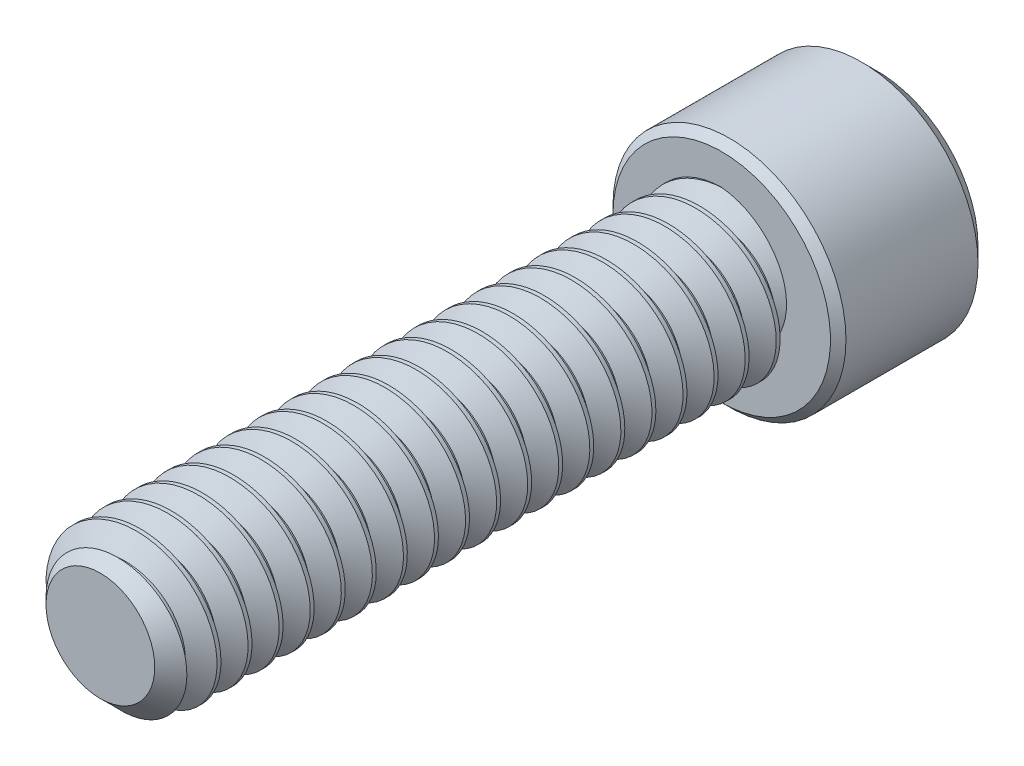
SolidWorks part; units mm, degrees
material "Plain Carbon Steel"
ref_plane "Front Plane" through (0, 0, 0) normal (0, 0, 1) x (1, 0, 0)
ref_plane "Top Plane" through (0, 0, 0) normal (0, 1, 0) x (1, 0, 0)
ref_plane "Right Plane" through (0, 0, 0) normal (1, 0, 0) x (0, 0, -1)
sketch "Sketch1" plane through (0, 0, 0) normal (0, 0, 1) x (1, 0, 0)
  line L0 (0, 3.175) -> (0, -3.175) construction
  circle A0 centre (0, 0) radius 3.175
  dimension "OD" = 6.35
extrude "Extrude1" add sketch "Sketch1" against normal blind 25.4
sketch "Sketch2" plane through (0, 0, 0) normal (0, 0, 1) x (1, 0, 0)
  circle A0 centre (0, 0) radius 3.175 construction
  circle A1 centre (0, 0) radius 3.175
curve "Helix/Spiral1" pitch 1.27 height 26.67 turns 21 parameters "pitch"=1.27
chamfer "Chamfer3" distance 0.9525 angle 45 1 edges at (3.175, 0, 0)
sketch "Sketch3" plane through (0, 0, 0) normal (1, 0, 0) x (0, 0, -1)
  line L0 (-1.1113, 3.175) -> (-0.635, 2.3501)
  line L1 (-0.635, 2.3501) -> (-0.4763, 2.3501)
  line L2 (-0.4763, 2.3501) -> (0, 3.175)
  line L3 (-1.1113, 3.175) -> (0, 3.175)
  line L4 (-0.5556, 3.175) -> (-0.5556, 2.3501) construction
  line L5 (-0.8731, 2.7626) -> (-0.2381, 2.7626) construction
  line L6 (0, 3.175) -> (0, -3.175) construction
  dimension "D1" = 0.1588
  dimension "D2" = 0.635
  dimension "D3" = 60
sweep "Cut-Sweep1" cut profiles "Sketch3" path "Helix/Spiral1"
sketch "Sketch6" plane through (0, 0, -25.4) normal (0, 0, -1) x (-1, 0, 0)
  circle A0 centre (0, 0) radius 4.7625
  dimension "head dia" = 9.525
extrude "Extrude2" add sketch "Sketch6" along normal blind 6.35
sketch "Sketch7" plane through (0, 0, -31.75) normal (0, 0, -1) x (-1, 0, 0)
  line L1 (0, 2.7496) -> (-2.3813, 1.3748)
  line L2 (-2.3813, 1.3748) -> (-2.3813, -1.3748)
  line L3 (-2.3813, -1.3748) -> (0, -2.7496)
  line L4 (0, -2.7496) -> (2.3813, -1.3748)
  line L5 (2.3813, -1.3748) -> (2.3813, 1.3748)
  line L6 (2.3813, 1.3748) -> (0, 2.7496)
  circle A0 centre (0, 0) radius 2.3813 construction
  dimension "hex dia" = 4.7625
extrude "Cut-Extrude1" cut sketch "Sketch7" against normal blind 3.5719
sketch "Sketch8" plane through (0, 0, -31.75) normal (0, 0, -1) x (-1, 0, 0)
  circle A0 centre (0, 0) radius 2.7496
extrude "Cut-Extrude2" cut sketch "Sketch8" against normal blind 0.635 draft 45
chamfer "Chamfer1" distance 0.635 angle 45 1 edges at (-4.7625, 0, -31.75)
chamfer "Chamfer2" distance 0.3175 angle 45 1 edges at (-4.7625, 0, -25.4)
sketch "Sketch9" plane through (0, 0, 0) normal (1, 0, 0) x (0, 0, -1)
  line L0 (0, 3.175) -> (0, -3.175) construction
  line L1 (6.985, 3.175) -> (6.985, -3.175) construction
  line L2 (25.4, 4.7625) -> (25.4, -4.7625) construction
  line L3 (31.75, 4.7625) -> (31.75, -4.7625) construction
  line L4 (31.75, 0) -> (0, 0) construction
  dimension "D1" = 6.985
  dimension "D2" = 6.35
  dimension "D3" = 9.525
  dimension "D4" = 25.4
equation "\"D3@Helix/Spiral1\" = \"screw length@Extrude1\"+\"pitch@Helix/Spiral1\""
equation "\"D1@Sketch3\" = \"pitch@Helix/Spiral1\"*.125"
equation "\"D2@Sketch3\" = \"pitch@Helix/Spiral1\"*.5"
equation "\"D1@Cut-Extrude1\" = \"hex dia@Sketch7\"*.75"
equation "\"D1@Chamfer1\" = \"head depth@Extrude2\"/10"
equation "\"D1@Sketch9\" = \"pitch@Helix/Spiral1\"*5.5"
equation "\"D1@Chamfer2\" = \"D1@Chamfer1\"/2"
equation "\"D1@Cut-Extrude2\" = \"D1@Chamfer2\"*2"
equation "\"D1@Chamfer3\" = \"pitch@Helix/Spiral1\"*.750"
equation "\"D2@Sketch9\" = \"head depth@Extrude2\""
equation "\"D3@Sketch9\" = \"head dia@Sketch6\""
equation "\"D4@Sketch9\" = \"screw length@Extrude1\""
